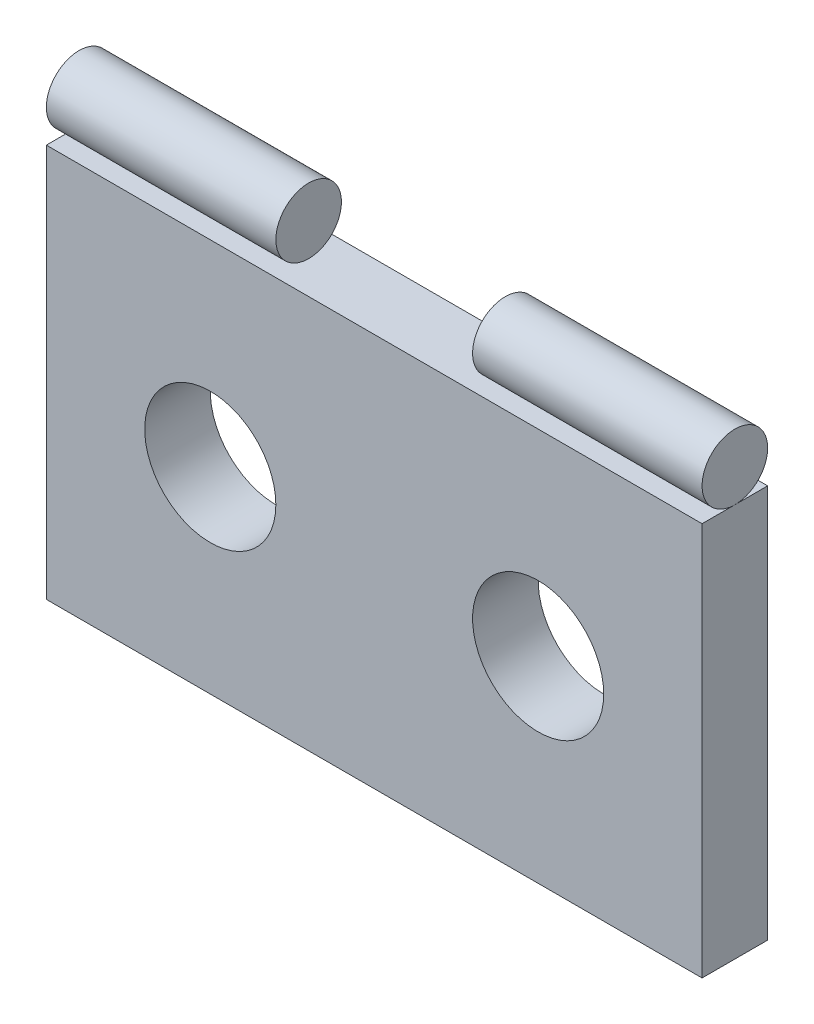
SolidWorks part; units mm, degrees
ref_plane "Plan de face" through (0, 0, 0) normal (0, 0, 1) x (1, 0, 0)
ref_plane "Plan de dessus" through (0, 0, 0) normal (0, 1, 0) x (1, 0, 0)
ref_plane "Plan de droite" through (0, 0, 0) normal (1, 0, 0) x (0, 0, -1)
sketch "Esquisse1" plane through (0, 0, 0) normal (0, 0, 1) x (1, 0, 0)
  line L1 (0, 0) -> (50, 0)
  line L2 (0, 0) -> (0, 30)
  line L3 (0, 30) -> (50, 30)
  line L4 (50, 0) -> (50, 30)
  dimension "D1" = 50
  dimension "D2" = 30
extrude "Boss.-Extru.1" add sketch "Esquisse1" along normal blind 5
sketch "Esquisse2" plane through (0, 0, 5) normal (0, 0, 1) x (1, 0, 0)
  line L0 (0, 15) -> (12.5, 15) construction
  line L1 (0, 30) -> (0, 0) construction
  line L2 (50, 15) -> (37.5, 15) construction
  line L3 (50, 0) -> (50, 30) construction
  circle A0 centre (12.5, 15) radius 5
  circle A1 centre (37.5, 15) radius 5
extrude "Enlèv. mat.-Extru.1" cut sketch "Esquisse2" against normal through all
sketch "Esquisse3" plane through (50, 0, 0) normal (1, 0, 0) x (0, 0, -1)
  line L0 (-2.5, 30) -> (-2.5, 32.5) construction
  line L1 (-5, 30) -> (0, 30) construction
  circle A0 centre (-2.5, 32.5) radius 2.5
  dimension "D1" = 2.5
extrude "Boss.-Extru.2" add sketch "Esquisse3" against normal blind 50 separate body
sketch "Esquisse4" plane through (0, 0, 5) normal (0, 0, 1) x (1, 0, 0)
  line L0 (17.5, 15) -> (17.5, 30) construction
  line L1 (50, 30) -> (0, 30) construction
  line L2 (32.5, 15) -> (32.5, 30) construction
  line L3 (50, 35) -> (0, 35) construction
  line L4 (17.5, 30) -> (32.5, 30)
  line L5 (17.5, 30) -> (17.5, 35)
  line L6 (17.5, 35) -> (32.5, 35)
  line L7 (32.5, 30) -> (32.5, 35)
  circle A0 centre (12.5, 15) radius 5 construction
  circle A1 centre (37.5, 15) radius 5 construction
extrude "Enlèv. mat.-Extru.4" cut sketch "Esquisse4" against normal blind 50 and the other way blind 50
